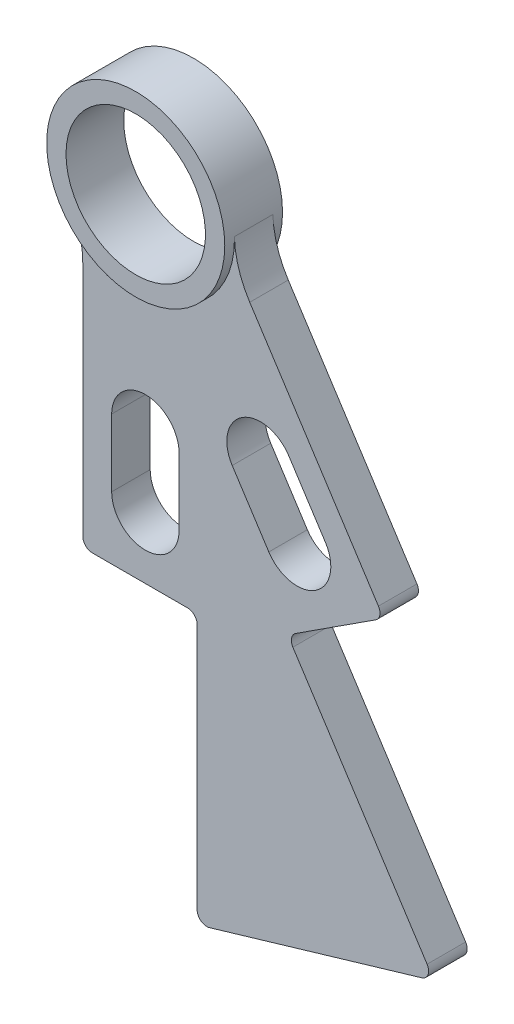
SolidWorks part; units mm, degrees
material "AISI 4130 Steel, annealed at 865C"
ref_plane "X-Y Datum" through (0, 0, 0) normal (0, 0, 1) x (1, 0, 0)
ref_plane "X-Z Datum" through (0, 0, 0) normal (0, 1, 0) x (1, 0, 0)
ref_plane "Y-Z Datum" through (0, 0, 0) normal (1, 0, 0) x (0, 0, -1)
sketch "Sketch1" plane through (0, 0, 0) normal (0, 0, 1) x (1, 0, 0)
  line L0 (0, -46.0556) -> (0, -34.9431) construction
  line L1 (-5.5563, -46.0556) -> (-5.5563, -34.9431)
  line L2 (5.5563, -46.0556) -> (5.5563, -34.9431)
  line L3 (25.0228, -38.6649) -> (18.9852, -29.3357) construction
  line L4 (20.3582, -41.6837) -> (14.3206, -32.3545)
  line L5 (29.6874, -35.6461) -> (23.6498, -26.3169)
  line L6 (-10.3187, -15.7343) -> (-10.3187, -56.3743)
  line L7 (-10.3187, -56.3743) -> (10.3188, -56.3743)
  line L10 (21.9663, -52.9341) -> (39.292, -41.7214)
  line L11 (39.292, -41.7214) -> (17.2116, -7.603)
  line L13 (8.5408, -100.8243) -> (47.6094, -89.2851)
  line L14 (0, -51.6118) -> (0, -56.3743) construction
  line L15 (28.0416, -43.3295) -> (30.6292, -47.3278) construction
  line L16 (26.6686, -30.9815) -> (30.6669, -28.3939) construction
  line L17 (-5.5563, -40.4993) -> (-10.3187, -40.4993) construction
  line L18 (-10.3187, -24.6243) -> (10.3187, -24.6243) construction
  line L19 (10.3187, -24.6243) -> (10.3188, -56.3743) construction
  line L20 (5.5563, -40.4993) -> (10.3188, -40.4993) construction
  line L21 (0, -29.3868) -> (0, -24.6243) construction
  line L22 (21.9663, -52.9341) -> (4.716, -26.2791) construction
  line L23 (4.716, -26.2791) -> (22.0417, -15.0664) construction
  line L24 (17.3394, -37.0191) -> (13.3411, -39.6066) construction
  line L25 (15.9664, -24.671) -> (13.3788, -20.6728) construction
  line L31 (8.5408, -56.3743) -> (8.5408, -100.8243)
  line L33 (23.459, -51.9681) -> (47.6094, -89.2851)
  line L34 (218.5438, -337.6911) -> (0, 0) construction
  line L35 (0, -404.7476) -> (0, 0) construction
  circle A0 centre (0, 0) radius 11.4954
  arc A1 (-5.5563, -46.0556) -> (5.5563, -46.0556) centre (0, -46.0556) ccw
  arc A2 (5.5563, -34.9431) -> (-5.5563, -34.9431) centre (0, -34.9431) ccw
  arc A3 (20.3582, -41.6837) -> (29.6874, -35.6461) centre (25.0228, -38.6649) ccw
  arc A4 (23.6498, -26.3169) -> (14.3206, -32.3545) centre (18.9852, -29.3357) ccw
  arc A5 (14.673, 0.4911) -> (-12.5852, -7.5598) centre (0, 0) ccw
  arc A6 (17.2116, -7.603) -> (14.673, 0.4911) centre (30.5391, 1.0221) cw
  arc A7 (-10.3187, -15.7343) -> (-12.5852, -7.5598) centre (-26.1937, -15.7343) ccw
  arc A14 (-12.5852, -7.5598) -> (14.673, 0.4911) centre (0, 0) ccw
  point P5 (0, -40.4993)
  point P11 (22.004, -34.0003)
  point P24 (30.6292, -47.3278)
  point P31 (0, -56.3743)
  point P37 (23.459, -51.9681)
  point P39 (28.0416, -43.3295)
  point P51 (8.5408, -56.3743)
  dimension "D1" = 22.9908
  dimension "D2" = 14.6812
  dimension "D8" = 15.875
  dimension "D9" = 1.778
  dimension "D3" = 1.778
  dimension "D4" = 4.7625
  dimension "D5" = 31.75
  dimension "D6" = 8.89
  dimension "D7" = 8.89
  dimension "D10" = 44.45
  dimension "D11" = 32.91
extrude "Boss-Extrude2" add sketch "Sketch1" along normal mid plane 9.525 contours A5 A14 A0 region at (-4.041, 13.6817, 0)
extrude "Boss-Extrude3" add sketch "Sketch1<4>" along normal mid plane 6.35 contours A14 A7 L6 L7 L10 L11 A6 A4 L5 A3 L4 A2 L2 A1 L1 region at (16.0353, -54.2913, 0)
sketch "Sketch1<4>" plane through (0, 0, 0) normal (0, 0, 1) x (1, 0, 0) same geometry as "Sketch1"
fillet "Fillet1" radius 1.5875 6 edges at (-10.3187, -56.3743, 0) (39.292, -41.7214, 0) (8.5408, -100.8243, 0) (47.6094, -89.2851, 0) (23.459, -51.9681, 0) (8.5408, -56.3743, 0)
sketch "Sketch2" plane through (0, 0, 4.7625) normal (0, 0, 1) x (1, 0, 0)
  point P0 (0, 0)
sketch "Sketch3" plane through (0, 0, -4.7625) normal (0, 0, -1) x (-1, 0, 0)
  point P0 (0, 0)
